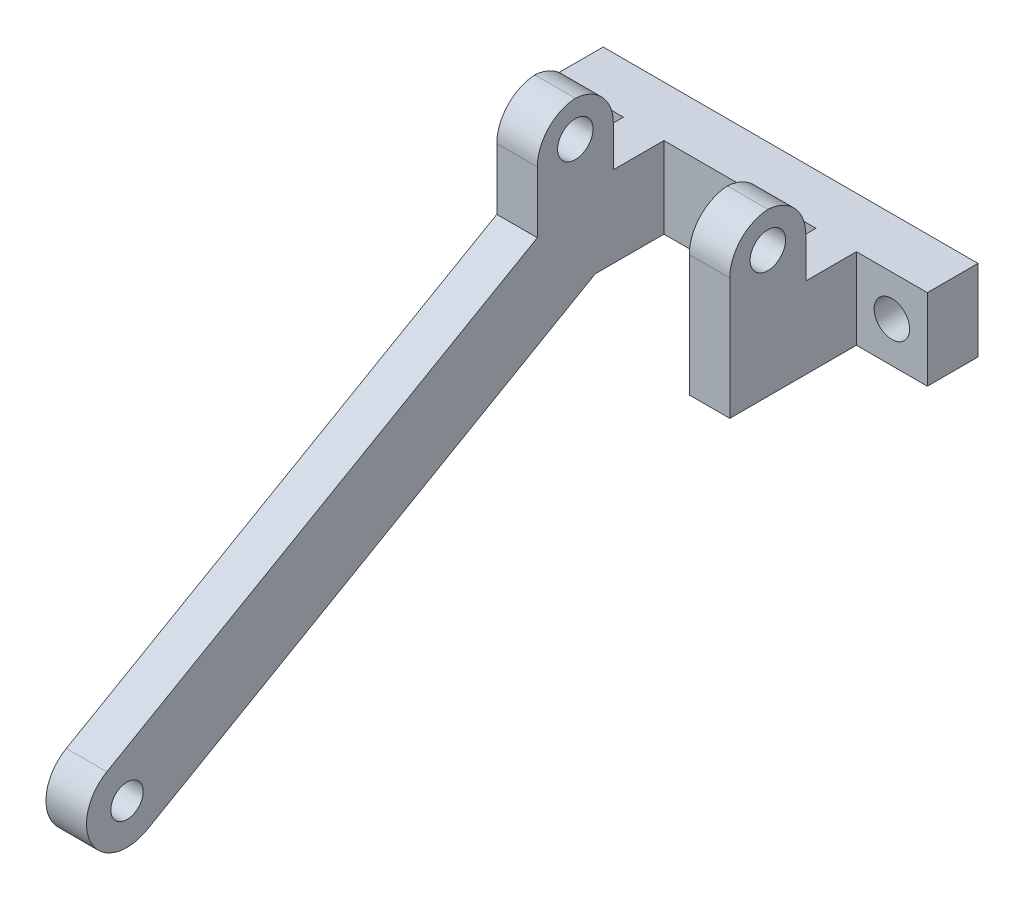
SolidWorks part; units mm, degrees
ref_plane "Front Plane" through (0, 0, 0) normal (0, 0, 1) x (1, 0, 0)
ref_plane "Top Plane" through (0, 0, 0) normal (0, 1, 0) x (1, 0, 0)
ref_plane "Right Plane" through (0, 0, 0) normal (1, 0, 0) x (0, 0, -1)
sketch "Sketch1" plane through (0, 0, 0) normal (0, 0, 1) x (1, 0, 0)
  line L0 (15, 0) -> (-15, 0) construction
  line L1 (-18.5, 4) -> (18.5, 4)
  line L2 (-18.5, 4) -> (-18.5, -4)
  line L3 (-18.5, -4) -> (18.5, -4)
  line L4 (18.5, 4) -> (18.5, -4)
  line L5 (-18.5, 4) -> (18.5, -4) construction
  line L6 (-18.5, -4) -> (18.5, 4) construction
  line L7 (0, -4) -> (0, 4) construction
  circle A0 centre (-15, 0) radius 1.75
  circle A1 centre (15, 0) radius 1.75
  point P0 (0, 0)
  point P12 (0, 0)
  dimension "D3" = 3.5
  dimension "D1" = 37
  dimension "D2" = 8
  dimension "D4" = 15
extrude "Boss-Extrude1" add sketch "Sketch1" along normal blind 5
sketch "Sketch2" plane through (0, 0, 5) normal (0, 0, 1) x (1, 0, 0)
  line L0 (0, 4) -> (0, -4) construction
  line L1 (18.5, 4) -> (-18.5, 4) construction
  line L2 (-18.5, -4) -> (18.5, -4) construction
  line L3 (11.5, -4) -> (7.5, 4) construction
  line L4 (-11.5, 4) -> (-7.5, 4)
  line L5 (-11.5, 4) -> (-11.5, -4)
  line L6 (-11.5, -4) -> (-7.5, -4)
  line L7 (-7.5, 4) -> (-7.5, -4)
  line L8 (-11.5, 4) -> (-7.5, -4) construction
  line L9 (-11.5, -4) -> (-7.5, 4) construction
  line L10 (11.5, 4) -> (7.5, -4) construction
  line L11 (7.5, 4) -> (7.5, -4)
  line L12 (11.5, -4) -> (7.5, -4)
  line L13 (11.5, 4) -> (11.5, -4)
  line L14 (11.5, 4) -> (7.5, 4)
  point P6 (-9.5, 0)
  point P15 (9.5, 0)
  dimension "D1" = 7.5
  dimension "D2" = 4
extrude "Boss-Extrude2" add sketch "Sketch2" along normal blind 12.5
sketch "Sketch4" plane through (0, 4, 0) normal (0, 1, 0) x (1, 0, 0)
  line L0 (-7.5, -17.5) -> (-7.5, -5) construction
  line L1 (-11.5, -17.5) -> (-7.5, -17.5)
  line L2 (-11.5, -17.5) -> (-11.5, -10)
  line L3 (-11.5, -10) -> (-7.5, -10)
  line L4 (-7.5, -17.5) -> (-7.5, -10)
  line L5 (0, 0) -> (0, -5) construction
  line L6 (7.5, -5) -> (-7.5, -5) construction
  line L7 (7.5, -17.5) -> (7.5, -10)
  line L8 (11.5, -10) -> (7.5, -10)
  line L9 (11.5, -17.5) -> (11.5, -10)
  line L10 (11.5, -17.5) -> (7.5, -17.5)
  dimension "D1" = 7.5
extrude "Boss-Extrude3" add sketch "Sketch4" along normal blind 8
sketch "Sketch3" plane through (-11.5, 0, 0) normal (-1, 0, 0) x (0, 0, 1)
  line L0 (10, 8.5) -> (17.5, 8.5) construction
  line L4 (10, 12) -> (10, 4) construction
  line L5 (17.5, 12) -> (17.5, -4) construction
  line L6 (13.75, 8.5) -> (13.75, 12) construction
  line L7 (10, 12) -> (17.5, 12) construction
  circle A0 centre (13.75, 8.5) radius 1.75
  dimension "D1" = 3.5
  dimension "D2" = 8.5
extrude "Cut-Extrude1" cut sketch "Sketch3" against normal through all
fillet "Fillet1" radius 4 4 edges at (-9.5, 12, 10) (9.5, 12, 10) (9.5, 12, 17.5) (-9.5, 12, 17.5)
sketch "Sketch5" plane through (-7.5, 0, 0) normal (1, 0, 0) x (0, 0, -1)
  line L0 (-10, 8) -> (-10, 4) construction
  line L1 (-10, 6.5) -> (-13, 6.5)
  line L2 (-10, 6.5) -> (-10, 1.5)
  line L3 (-10, 1.5) -> (-13, 1.5)
  line L4 (-13, 6.5) -> (-13, 1.5)
  line L5 (-10, 4) -> (-5, 4) construction
  dimension "D1" = 3
  dimension "D2" = 5
  dimension "D3" = 2.5
extrude "Boss-Extrude4" [suppressed] add sketch "Sketch5" along normal up to next
sketch "Sketch6" plane through (-11.5, 0, 0) normal (-1, 0, 0) x (0, 0, 1)
  line L0 (56.0113, -29.4012) -> (11.7824, -4)
  line L1 (17.5, -4) -> (5, -4) construction
  line L2 (11.7824, -4) -> (17.5, 1.9418)
  line L3 (13.75, 8.5) -> (58.0033, -25.9326) construction
  line L4 (17.5, 1.9418) -> (59.9954, -22.4639)
  line L5 (59.9954, -22.4639) -> (56.0113, -29.4012) construction
  line L6 (13.75, 8.5) -> (13.75, -4) construction
  line L7 (17.5, 8) -> (17.5, -4) construction
  circle A0 centre (58.0033, -25.9326) radius 1.6
  arc A1 (56.0113, -29.4012) -> (59.9954, -22.4639) centre (58.0033, -25.9326) ccw
  dimension "D1" = 3.2
  dimension "D2" = 8
  dimension "D3" = 52.114
  dimension "D4" = 56.071
  dimension "D5" = 1.9676
extrude "Boss-Extrude5" add sketch "Sketch6" against normal up to surface (4 mm away) up to face at (-7.5, 6.75, 13.75)
equation "\"X-ROD-SPACING\"=45"
equation "\"Y-ROD-SPACING\"=75"
equation "\"Z-ROD-SPACING\"=17.5"
equation "\"Y-BED-OFFSET\"=2"
equation "\"Y-BED-ROD-INSET\"=3.5"
equation "\"Y-BED-SCREW-SPACING\"=209"
equation "\"Y-BED-SCREW-CUTOUT-SLOT-HEIGHT\"=2.5"
equation "\"T-SLOT-NUT-FILLET-RADIUS\"=0.5"
equation "\"T-SLOT-SCREW-SHAFT-RADIUS\"=1.55"
equation "\"T-SLOT-SCREW-SHAFT-CUTOUT-LENGTH\"=11"
equation "\"T-SLOT-NUT-DEPTH\"=3.5"
equation "\"T-SLOT-NUT-WIDTH\"=2.85"
equation "\"T-SLOT-NUT-END-DISTANCE\"=8"
equation "\"ACRYLIC-THICKNESS\"=10"
equation "\"ACRYLIC-THICKNESS2\"=4.5"
equation "\"ACRYLIC-TAB-CUTOUT-SIZE\"=\"ACRYLIC-THICKNESS\"+\"ACRYLIC-TAB-TOLERANCE\"*2"
equation "\"ACRYLIC-TAB-TOLERANCE\"=-.05"
equation "\"ACRYLIC-TAB-WIDTH\"=\"ACRYLIC-THICKNESS\""
equation "\"ACRYLIC-M3-HOLE\"=2.9"
equation "\"SMOOTHROD-CAP-SCREW-DISTANCE\"=20"
equation "\"FRAME-WIDTH-INNER\"=370"
equation "\"NEMA17-HOLE-SPACING\"=31"
equation "\"NEMA17-CENTRAL-CUTOUT\"=22.5"
equation "\"Z-BRACKET-REACH\"=57"
equation "\"Z-ROD-INSET\"=13.5"
equation "\"TOP-BRACKET-SPACING\"=40"
equation "\"SMOOTHROD-X-LENGTH\"=350"
equation "\"SMOOTHROD-Y-LENGTH\"=350"
equation "\"SMOOTHROD-Z-LENGTH\"=350"
equation "\"SMOOTHROD-TIGHTENING-HEADROOM\"=.25"
equation "\"LEADSCREW-Z-LENGTH\"=300"
equation "\"SCREW-LENGTH-FRAME\"=\"ACRYLIC-THICKNESS\" + 10"
equation "\"SCREW-LENGTH-MOTOR\"=\"ACRYLIC-THICKNESS\" + 5"
equation "\"SCREW-LENGTH-EXTRUDER\"=28"
equation "\"SCREW-HEAD-RADIUS\"=6"
equation "\"PRINTED-X-SMOOTHROD-DIAMETER\"=8.8"
equation "\"PRINTED-X-SMOOTHROD-CUTOUT\"=10"
equation "\"PRINTED-X-BASE-HEIGHT\"=10"
equation "\"PRINTED-LM8UU-CUTOUT-SIZE\"=15.5"
equation "\"PRINTED-LM8UU-CUTOUT-LENGTH\"=24.5"
equation "\"PRINTED-X-IDLER-HEIGHT\"=16"
equation "\"PSU-MOUNTING-WIDTH\"=95"
equation "\"PSU-MOUNTING-HEIGHT\"=177"
equation "\"Y-BELT-TO-ROD-DISTANCE\"=20"
equation "\"SPOOL-HOLDER-ROD-SPACING\"=150"
equation "\"ACRYLIC-X-CARRIAGE-WIDTH\"=55"
equation "\"ACRYLIC-X-CARRIAGE-HEIGHT\"=75"
equation "\"ACRYLIC-X-CARRIAGE-LM8UU-CUTOUT-WIDTH\"=24.25"
equation "\"ACRYLIC-X-CARRIAGE-LM8UU-CUTOUT-HEIGHT\"=11.0"
equation "\"ACRYLIC-X-CARRIAGE-SCREW-SPACING-X\"=15"
equation "\"ACRYLIC-X-CARRIAGE-SCREW-SPACING-Y\"=33"
equation "\"ACRYLIC-X-CARRIAGE-CENTER-TAB-SPACING\"=14"
equation "\"ACRYLIC-X-CARRIAGE-EXTRUDER-OFFSET\"=26"
equation "\"ACRYLIC-X-CARRIAGE-EXTRUDER-ANGLE\"=90"
equation "\"ACRYLIC-X-CARRIAGE-EXTRUDER-SHELF-DEPTH\"=\"ACRYLIC-X-CARRIAGE-EXTRUDER-OFFSET\" + 28"
equation "\"ACRYLIC-X-CARRIAGE-EXTRUDER-BRACE-SPACING\"=23"
equation "\"ACRYLIC-X-CARRIAGE-EXTRUDER-BRACE-TAB-OFFSET\"=20"
equation "\"ACRYLIC-X-CARRIAGE-EXTRUDER-BRACE-HEIGHT\"=35"
equation "\"ACRYLIC-X-CARRIAGE-EXTRUDER-BRACE-SCREW-SPACING\"=22"
equation "\"ACRYLIC-X-CARRIAGE-DUAL-WIDTH-MULTIPLIER\"=1.65"
equation "\"ACRYLIC-X-CARRIAGE-DUAL-HOTEND-SPACING\"=42"
equation "\"ACRYLIC-X-CARRIAGE-DUAL-WIDTH\"=75"
equation "\"ACRYLIC-X-CARRIAGE-DUAL-HOTEND-SEPARATION\"=36"
equation "\"ACRYLIC-X-CARRIAGE-DUAL-MOUNT-PLATE-DEPTH\"=75"
equation "\"ACRYLIC-X-CARRIAGE-DUAL-MOUNT-BRACE-WIDTH\"=33"
equation "\"ACRYLIC-X-CARRIAGE-DUAL-MOUNT-SCREW-WIDTH\"=40"
equation "\"D3@Sketch1\"=3.5"
equation "\"PRINTED-M3-HOLE\"=3.5"
equation "\"BLOWER-FAN-WIDTH\"=15"
equation "\"D1@Sketch2\"=\"BLOWER-FAN-WIDTH\"/2"
